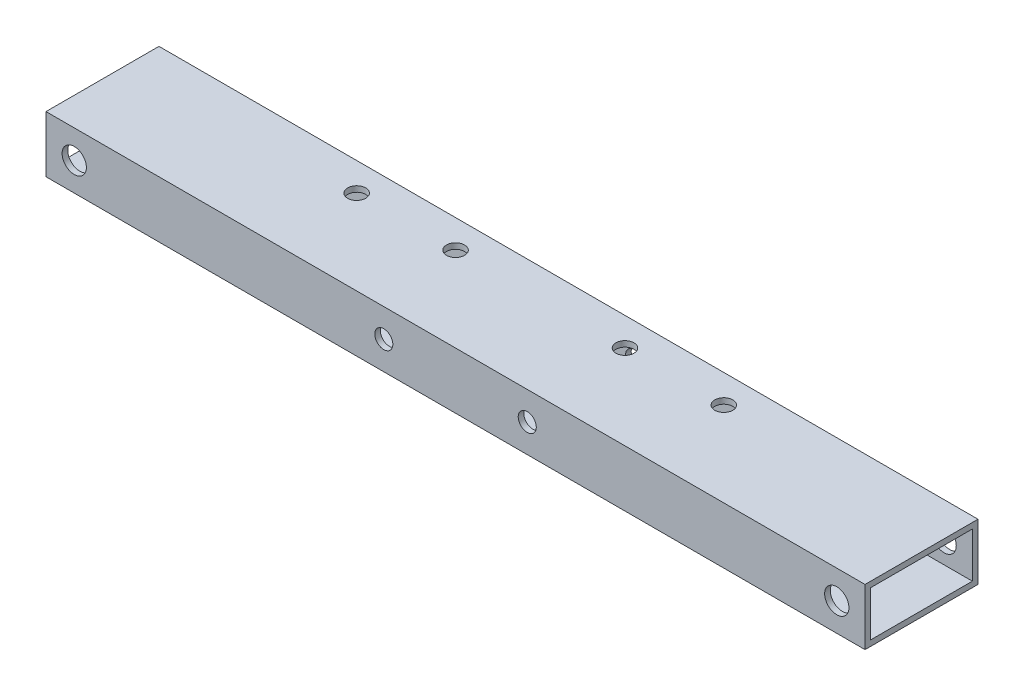
SolidWorks part; units mm, degrees
material "5052-H34"
ref_plane "正面" through (0, 0, 0) normal (0, 0, 1) x (1, 0, 0)
ref_plane "平面" through (0, 0, 0) normal (0, 1, 0) x (1, 0, 0)
ref_plane "右側面" through (0, 0, 0) normal (1, 0, 0) x (0, 0, -1)
sketch "ｽｹｯﾁ1" plane through (0, 0, 0) normal (1, 0, 0) x (0, 0, -1)
  line L1 (-10, 5) -> (10, 5)
  line L2 (-10, 5) -> (-10, -5)
  line L3 (-10, -5) -> (10, -5)
  line L4 (10, 5) -> (10, -5)
  line L5 (-10, 5) -> (10, -5) construction
  line L6 (-10, -5) -> (10, 5) construction
  point P0 (0, 0)
  dimension "D1" = 20
  dimension "D2" = 10
extrude "押し出し-薄板1" add sketch "ｽｹｯﾁ1" along normal blind 145 thin thin type one direction reverse wall 1
sketch "ｽｹｯﾁ2" plane through (0, 0, 10) normal (0, 0, 1) x (1, 0, 0)
  line L0 (72.5, 5) -> (72.5, -5) construction
  line L1 (145, 5) -> (0, 5) construction
  line L2 (145, -5) -> (0, -5) construction
  line L3 (145, 0) -> (140, 0) construction
  line L4 (145, 5) -> (145, -5) construction
  line L5 (72.5, 0) -> (85.2, 0) construction
  circle A0 centre (140, 0) radius 2.15
  circle A1 centre (85.2, 0) radius 1.6
  circle A2 centre (5, 0) radius 2.15
  circle A3 centre (59.8, 0) radius 1.6
  dimension "D2" = 4.3
  dimension "D3" = 3.2
  dimension "D1" = 5
  dimension "D4" = 25.4
extrude "ｶｯﾄ - 押し出し1" cut sketch "ｽｹｯﾁ2" against normal through all
sketch "ｽｹｯﾁ3" plane through (0, 5, 0) normal (0, 1, 0) x (1, 0, 0)
  line L0 (72.5, 10) -> (72.5, -10) construction
  line L1 (145, 10) -> (0, 10) construction
  line L2 (145, -10) -> (0, -10) construction
  line L3 (145, 5) -> (105, 5) construction
  line L4 (145, 10) -> (145, -10) construction
  circle A4 centre (105, 5) radius 1.6
  circle A5 centre (40, 5) radius 1.6
  circle A9 centre (87.5, 5) radius 1.6
  circle A10 centre (57.5, 5) radius 1.6
  point P10 (145, 4.6564)
  point P11 (0, 0)
  point P15 (0, 0)
  point P16 (0, 0)
  dimension "D1" = 3.2
  dimension "D4" = 5
  dimension "D2" = 17.5
  dimension "D3" = 30
extrude "ｶｯﾄ - 押し出し2" cut sketch "ｽｹｯﾁ3" against normal through all
